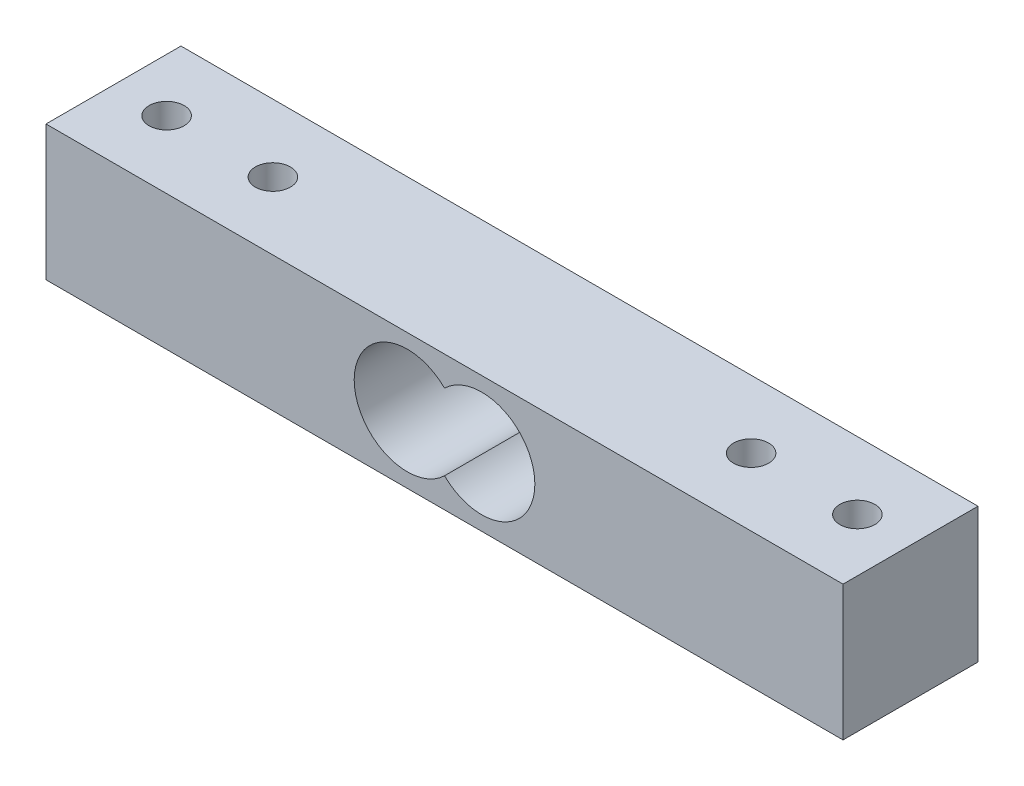
SolidWorks part; units mm, degrees
ref_plane "Ebene vorne" through (0, 0, 0) normal (0, 0, 1) x (1, 0, 0)
ref_plane "Ebene oben" through (0, 0, 0) normal (0, 1, 0) x (1, 0, 0)
ref_plane "Ebene rechts" through (0, 0, 0) normal (1, 0, 0) x (0, 0, -1)
sketch "Skizze2" plane through (0, 0, 0) normal (0, 1, 0) x (1, 0, 0)
  line L1 (-37.5, -6.35) -> (37.5, -6.35)
  line L2 (-37.5, -6.35) -> (-37.5, 6.35)
  line L3 (-37.5, 6.35) -> (37.5, 6.35)
  line L4 (37.5, -6.35) -> (37.5, 6.35)
  line L5 (-37.5, -6.35) -> (37.5, 6.35) construction
  line L6 (-37.5, 6.35) -> (37.5, -6.35) construction
  line L8 (-41.25, 0) -> (41.25, 0) construction
  line L9 (0, -6.985) -> (0, 6.985) construction
  circle A2 centre (-22.5, 0) radius 1.65
  circle A3 centre (-32.5, 0) radius 1.65
  circle A4 centre (22.5, 0) radius 1.65
  circle A5 centre (32.5, 0) radius 1.65
  point P0 (0, 0)
  dimension "D3" = 12.7
  dimension "D4" = 10
  dimension "D1" = 5
  dimension "D2" = 75
extrude "Aufsatz-Linear austragen1" add sketch "Skizze2" along normal blind 6.35 and the other way blind 6.35
sketch "Skizze3" plane through (0, 0, 0) normal (0, 0, 1) x (1, 0, 0)
  line L0 (6.985, 0) -> (-6.985, 0) construction
  line L1 (0, -6.985) -> (0, 6.985) construction
  arc A0 (0, 3.5707) -> (0, -3.5707) centre (-3.5, 0) ccw
  arc A1 (0, 3.5707) -> (0, -3.5707) centre (3.5, 0) cw
  dimension "D1" = 10
  dimension "D2" = 3.5
extrude "Schnitt-Linear austragen2" cut sketch "Skizze3" along direction (0, 0, 1) on the side against the normal through all both and the other way through all
ref_plane "Ebene1" through (0, 0, 0) normal (0, 1, 0) x (1, 0, 0)
sketch "Skizze4" plane through (0, 0, 0) normal (0, 1, 0) x (1, 0, 0)
  line L4 (-37.5, -6.35) -> (37.5, -6.35)
  line L5 (-37.5, -6.35) -> (-37.5, 6.35)
  line L6 (-37.5, 6.35) -> (37.5, 6.35)
  line L7 (37.5, -6.35) -> (37.5, 6.35)
  line L8 (-37.5, -6.35) -> (37.5, 6.35) construction
  line L9 (-37.5, 6.35) -> (37.5, -6.35) construction
  circle A0 centre (22.5, 0) radius 1.65
  circle A1 centre (32.5, 0) radius 1.65
  circle A2 centre (-32.5, 0) radius 1.65
  circle A3 centre (-22.5, 0) radius 1.65
  point P8 (0, 0)
